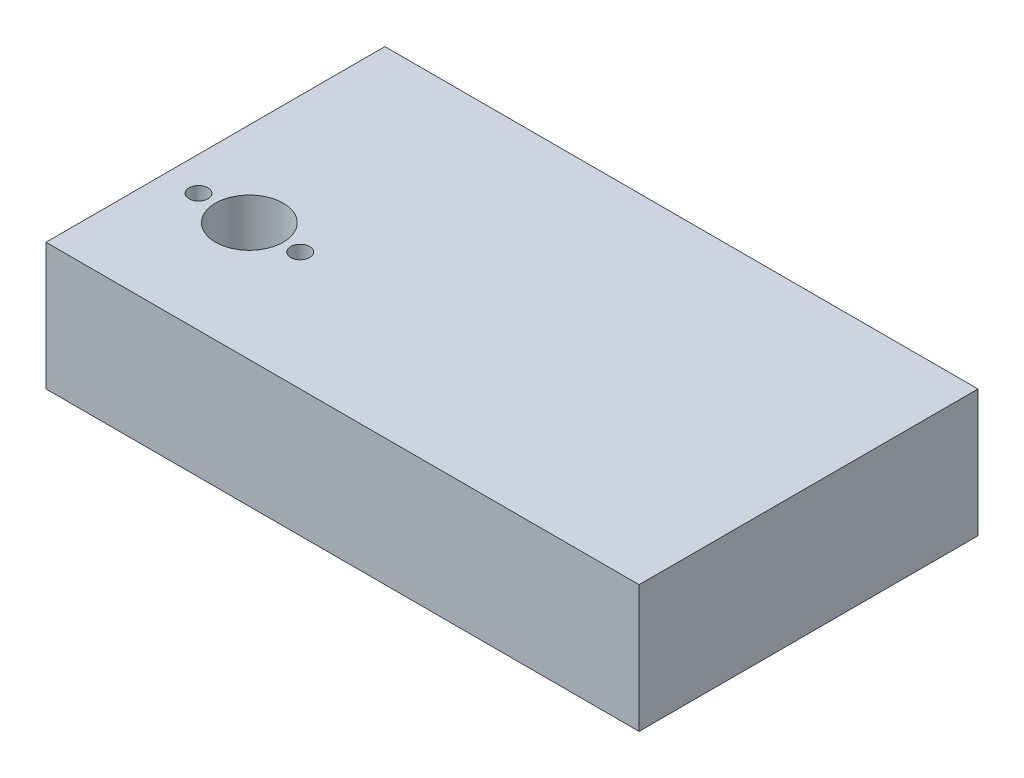
SolidWorks part; units mm, degrees
ref_plane "Front Plane" through (0, 0, 0) normal (0, 0, 1) x (1, 0, 0)
ref_plane "Top Plane" through (0, 0, 0) normal (0, 1, 0) x (1, 0, 0)
ref_plane "Right Plane" through (0, 0, 0) normal (1, 0, 0) x (0, 0, -1)
sketch "Sketch1" plane through (0, 0, 0) normal (0, 0, 1) x (1, 0, 0)
  line L1 (-45.1303, 23.1413) -> (94.8697, 23.1413)
  line L2 (-45.1303, 23.1413) -> (-45.1303, -6.8587)
  line L3 (-45.1303, -6.8587) -> (94.8697, -6.8587)
  line L4 (94.8697, 23.1413) -> (94.8697, -6.8587)
  dimension "D1" = 140
  dimension "D2" = 30
extrude "Boss-Extrude1" add sketch "Sketch1" along normal blind 80
sketch "Sketch2" plane through (0, 0, 0) normal (0, 0, -1) x (-1, 0, 0)
  line L0 (45.1303, -6.8587) -> (-94.8697, -6.8587) construction
  line L1 (45.1303, 23.1413) -> (45.1303, -6.8587) construction
  circle A0 centre (30.1303, 7.8145) radius 4.1759
  dimension "D1" = 14.6732
  dimension "D2" = 15
extrude "Cut-Extrude1" cut sketch "Sketch2" against normal blind 15
pattern_linear "LPattern1" count 4 spacing 110 along (1, 0, 0) of "Cut-Extrude1"
sketch "Эскиз1" plane through (0, -6.8587, 0) normal (0, -1, 0) x (1, 0, 0)
  line L0 (-45.1303, 80) -> (-45.1303, 0) construction
  line L1 (-45.1303, 0) -> (94.8697, 0) construction
  circle A0 centre (-5.1303, 33) radius 25
  dimension "D3" = 50
  dimension "D1" = 40
  dimension "D2" = 33
extrude "Вырез-Вытянуть1" cut sketch "Эскиз1" against normal blind 10.5
sketch "Эскиз2" plane through (0, 3.6413, 0) normal (0, -1, 0) x (1, 0, 0)
  circle A0 centre (-5.1303, 33) radius 5
  circle A1 centre (-5.1303, 33) radius 25 construction
extrude "Вырез-Вытянуть2" cut sketch "Эскиз2" against normal blind 10.5
sketch "Эскиз3" plane through (0, -6.8587, 0) normal (0, -1, 0) x (1, 0, 0)
  line L0 (-45.1303, 80) -> (-45.1303, 0) construction
  line L1 (-45.1303, 80) -> (94.8697, 80) construction
  circle A0 centre (-25.1303, 52) radius 8
  dimension "D3" = 16
  dimension "D1" = 20
  dimension "D2" = 28
extrude "Вырез-Вытянуть3" cut sketch "Эскиз3" against normal blind 100
sketch "Эскиз4" plane through (0, -6.8587, 0) normal (0, -1, 0) x (1, 0, 0)
  circle A0 centre (-25.1303, 52) radius 10
extrude "Вырез-Вытянуть4" cut sketch "Эскиз4" against normal blind 10.5
sketch "Эскиз5" plane through (0, 23.1413, 0) normal (0, 1, 0) x (1, 0, 0)
  line L1 (94.8697, -80) -> (-45.1303, -80) construction
  circle A0 centre (-37.1303, -52) radius 2.25
  circle A1 centre (-25.1303, -52) radius 8 construction
  point P4 (0, 0)
  point P6 (-38.3272, -52.6704)
  dimension "D1" = 12
  dimension "D2" = 28
  dimension "D3" = 4.5
extrude "Вырез-Вытянуть5" cut sketch "Эскиз5" against normal blind 10.5
pattern_linear "Линейный массив1" count 2 spacing 24 along (1, 0, 0) of "Вырез-Вытянуть5"
